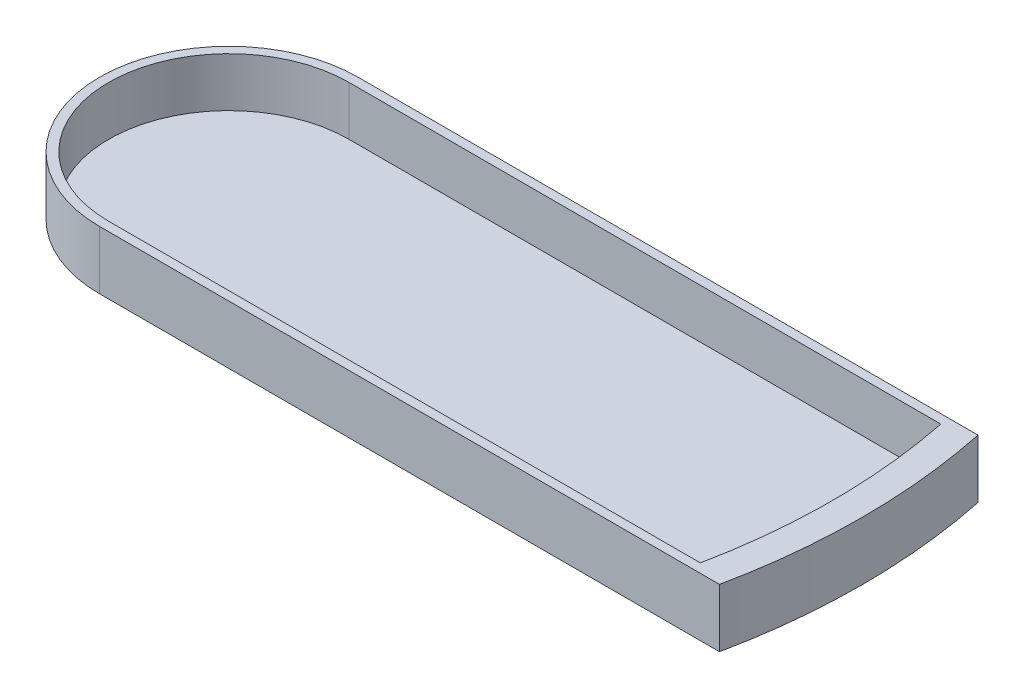
SolidWorks part; units mm, degrees
material "6061-T6 (SS)"
ref_plane "Front" through (0, 0, 0) normal (0, 0, 1) x (1, 0, 0)
ref_plane "Top" through (0, 0, 0) normal (0, 1, 0) x (1, 0, 0)
ref_plane "Right" through (0, 0, 0) normal (1, 0, 0) x (0, 0, -1)
sketch "Sketch1" plane through (0, 0, 0) normal (0, 1, 0) x (1, 0, 0)
  line L0 (0, 28.575) -> (137.0528, 28.575)
  line L1 (0, -28.575) -> (137.0528, -28.575)
  line L3 (0, -26.575) -> (130.8282, -26.575)
  line L7 (0, 26.575) -> (130.8282, 26.575)
  arc A0 (133.5, 0) -> (130.8282, -26.575) centre (0, 0) cw
  arc A1 (0, 26.575) -> (0, -26.575) centre (0, 0) ccw
  arc A2 (133.5, 0) -> (130.8282, 26.575) centre (0, 0) ccw
  arc A3 (0, 28.575) -> (0, -28.575) centre (0, 0) ccw
  arc A4 (140, 0) -> (137.0528, 28.575) centre (0, 0) ccw
  arc A5 (140, 0) -> (137.0528, -28.575) centre (0, 0) cw
extrude "Boss-Extrude2" add sketch "Sketch1" against normal blind 2 contours A3 L1 A5 A4 L0
extrude "Boss-Extrude3" add sketch "Sketch1<14>" along normal blind 10.9 contours L3 A0 A2 L7 A1 | L1 A5 A4 L0 A3
sketch "Sketch1<14>" plane through (0, 0, 0) normal (0, 1, 0) x (1, 0, 0) same geometry as "Sketch1"
